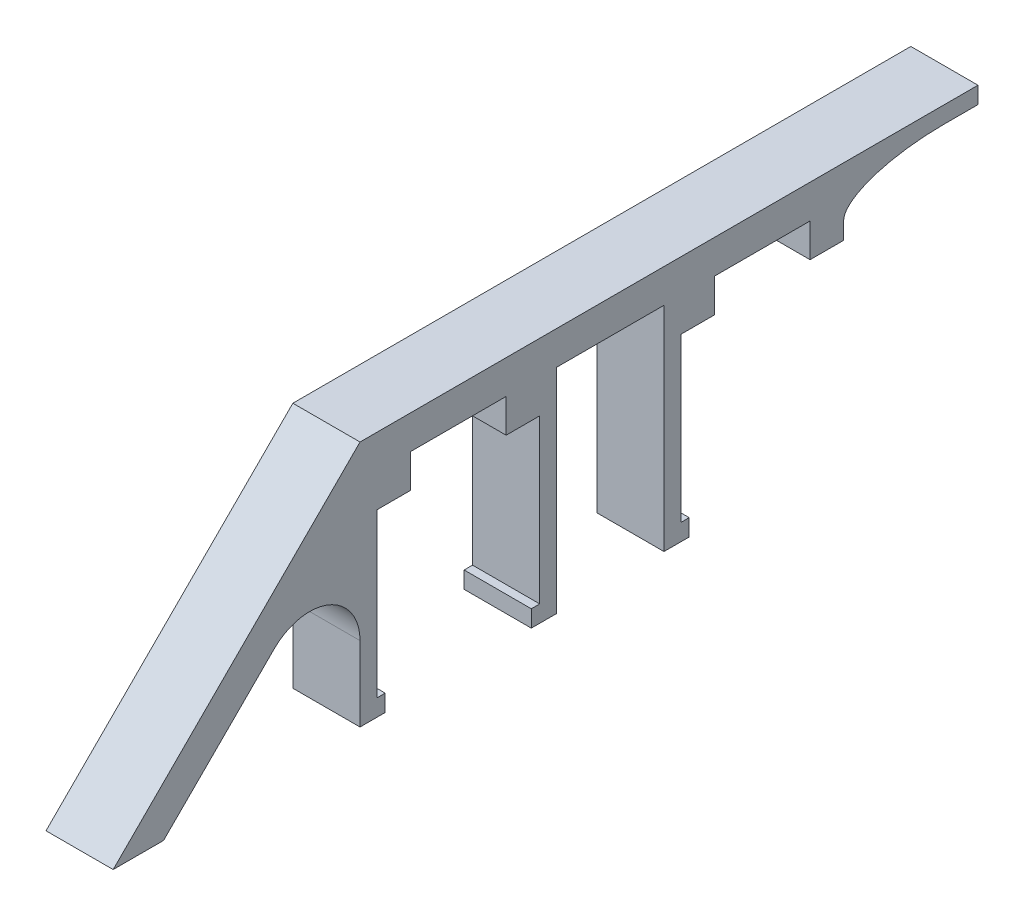
SolidWorks part; units mm, degrees
ref_plane "Front" through (0, 0, 0) normal (0, 0, 1) x (1, 0, 0)
ref_plane "Top" through (0, 0, 0) normal (0, 1, 0) x (1, 0, 0)
ref_plane "Right" through (0, 0, 0) normal (1, 0, 0) x (0, 0, -1)
sketch "Sketch1" plane through (0, 0, 0) normal (1, 0, 0) x (0, 0, -1)
  line L16 (-5, 68.5) -> (-5, -5)
  line L17 (-5, -5) -> (2.5, -5)
  line L18 (2.5, -5) -> (2.5, 0)
  line L19 (2.5, 0) -> (0, 0)
  line L20 (0, 0) -> (0, 48.5)
  line L21 (0, 48.5) -> (10, 48.5)
  line L22 (10, 48.5) -> (10, 58.5)
  line L23 (10, 58.5) -> (38.5, 58.5)
  line L24 (38.5, 58.5) -> (38.5, 48.5)
  line L25 (38.5, 48.5) -> (48.5, 48.5)
  line L26 (48.5, 48.5) -> (48.5, 0)
  line L27 (48.5, 0) -> (53.5, 0)
  line L28 (53.5, 0) -> (53.5, 58.5)
  line L29 (53.5, 58.5) -> (85.5, 58.5)
  line L30 (69.5, 58.5) -> (69.5, 90.1855)
  line L31 (-5, 68.5) -> (144, 68.5)
  line L32 (85.5, 0) -> (85.5, 58.5)
  line L33 (90.5, 0) -> (85.5, 0)
  line L34 (90.5, 48.5) -> (90.5, 0)
  line L35 (100.5, 48.5) -> (90.5, 48.5)
  line L36 (100.5, 58.5) -> (100.5, 48.5)
  line L37 (129, 58.5) -> (100.5, 58.5)
  line L38 (129, 48.5) -> (129, 58.5)
  line L39 (139, 48.5) -> (129, 48.5)
  line L40 (139, 0) -> (139, 48.5)
  line L41 (136.5, 0) -> (139, 0)
  line L42 (136.5, -5) -> (136.5, 0)
  line L43 (144, -5) -> (136.5, -5)
  line L44 (144, 68.5) -> (144, -5)
  line L45 (48.5, 0) -> (46, 0)
  line L46 (46, 0) -> (46, -5)
  line L47 (53.5, 0) -> (53.5, -5)
  line L48 (53.5, -5) -> (46, -5)
  line L49 (85.5, 0) -> (85.5, -5)
  line L50 (85.5, -5) -> (93, -5)
  line L51 (93, 0) -> (93, -5)
  line L52 (90.5, 0) -> (93, 0)
  line L53 (90.5, 0) -> (85.5, 0)
  line L54 (139, 48.5) -> (139, 68.5)
  line L55 (-5, 68.5) -> (-78.5, -5)
  line L56 (-5, -5) -> (-78.5, -5)
  line L57 (-78.5, -5) -> (-63.5, -5)
  line L58 (-63.5, -5) -> (-5, 53.5)
  line L59 (139, 63.5) -> (179, 63.5)
  line L60 (179, 63.5) -> (179, 68.5)
  line L61 (179, 68.5) -> (144, 68.5)
  point P9 (51, 0)
  point P32 (69.5, 68.5)
  dimension "D1" = 20
  dimension "D2" = 20
  dimension "D3" = 2.5
  dimension "D4" = 5
  dimension "D5" = 48.5
  dimension "D6" = 42
  dimension "D7" = 10
  dimension "D8" = 10
  dimension "D9" = 5
  dimension "D10" = 48.5
  dimension "D11" = 48.5
  dimension "D12" = 5
  dimension "D13" = 5
  dimension "D14" = 2.5
  dimension "D15" = 45
  dimension "D16" = 90
  dimension "D17" = 15
  dimension "D18" = 10
  dimension "D19" = 0
  dimension "D20" = 15
  dimension "D21" = 35
  dimension "D22" = 5
extrude "Boss-Extrude2" add sketch "Sketch1" along normal blind 20 contours L56 L58 L16 L55 | L31 L16 L17 L18 L19 L20 L21 L22 L23 L24 L25 L26 L27 L28 L29 L30 | L39 L54 L31 L30 L29 L32 L33 L34 L35 L36 L37 L38 | L52 L33 L49 L50 L51 | L48 L47 L27 L45 L46 | L44 L31 L54 | L60 L61 L44 region at (0, 67.4535, -32.25) region at (0, 28.142, 38.142) region at (0, 67.5242, -104.25) region at (0, 66, -141.5) region at (0, 66, -161.5) region at (0, -2.5, -49.75) region at (0, -2.5, -89.25)
fillet "Fillet1" radius 15 1 edges at (10, 53.5, 5)
fillet "Fillet2" radius 10 1 edges at (10, 63.5, -139) second distance 30 first distance on face at (10, 56, -139)
